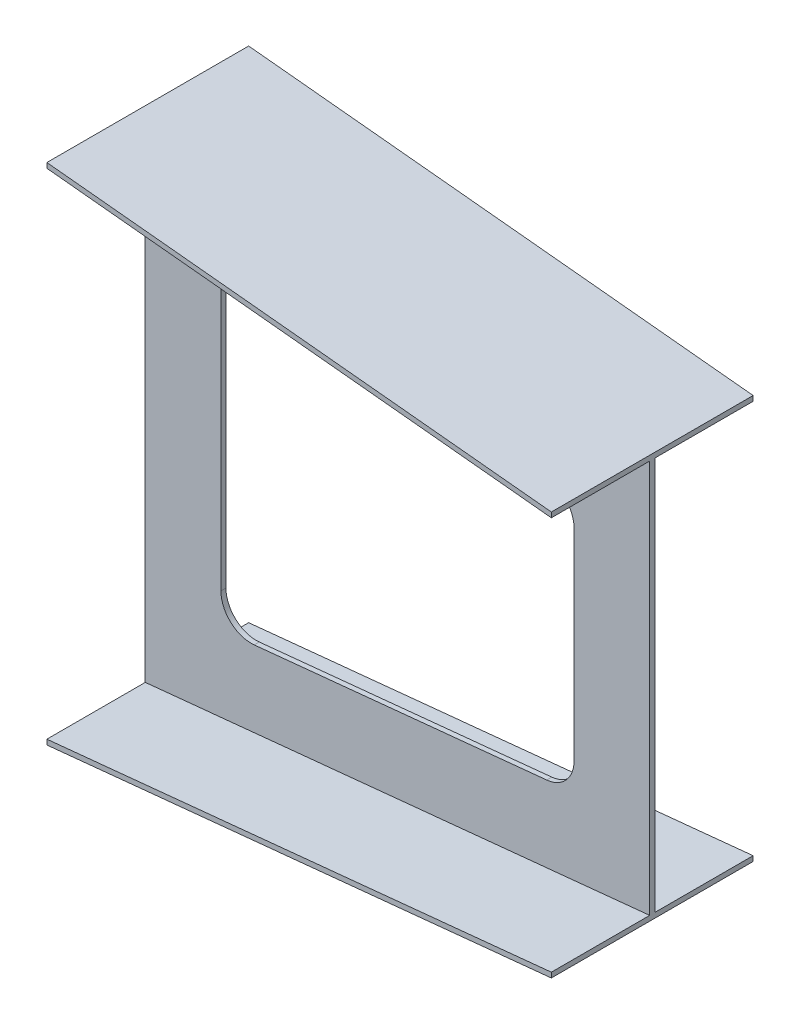
SolidWorks part; units mm, degrees
ref_plane "Front Plane" through (0, 0, 0) normal (0, 0, 1) x (1, 0, 0)
ref_plane "Top Plane" through (0, 0, 0) normal (0, 1, 0) x (1, 0, 0)
ref_plane "Right Plane" through (0, 0, 0) normal (1, 0, 0) x (0, 0, -1)
sketch "Sketch1" plane through (0, 0, 0) normal (1, 0, 0) x (0, 0, -1)
  line L1 (-205, 500) -> (195, 500)
  line L2 (-205, 500) -> (-205, 490)
  line L4 (195, 500) -> (195, 490)
  line L6 (-205, -490) -> (-205, -500)
  line L7 (-205, -500) -> (195, -500)
  line L8 (195, -490) -> (195, -500)
  line L15 (-205, -490) -> (-10, -490)
  line L16 (-5, 490) -> (-5, -490) construction
  line L18 (-205, 490) -> (-10, 490)
  line L19 (0, 0) -> (192.2403, 0) construction
  line L21 (-10, 490) -> (-10, -490)
  line L23 (0, 490) -> (0, -490)
  line L27 (0, 490) -> (195, 490)
  line L28 (0, -490) -> (195, -490)
  dimension "D1" = 400
  dimension "D2" = 10
  dimension "D3" = 1000
  dimension "D4" = 10
ref_plane "Plane2" through (1000, 0, 0) normal (1, 0, 0) x (0, 0, -1)
sketch "Sketch4" plane through (1000, 0, -1000) normal (-1, 0, 0) x (0, 0, 1)
  line L1 (805, 400) -> (1205, 400)
  line L2 (805, 400) -> (805, 390)
  line L4 (1205, 400) -> (1205, 390)
  line L6 (805, -390) -> (805, -400)
  line L7 (805, -400) -> (1205, -400)
  line L8 (1205, -390) -> (1205, -400)
  line L15 (805, -390) -> (1000, -390)
  line L16 (1005, 390) -> (1005, -390) construction
  line L18 (805, 390) -> (1000, 390)
  line L19 (1010, -390) -> (1205, -390)
  line L21 (1000, 390) -> (1000, -390)
  line L23 (1010, 390) -> (1010, -390)
  line L24 (1010, 390) -> (1205, 390)
  line L26 (1010, 490) -> (1010, -490) construction
  line L27 (1000, 0) -> (820.2065, 0) construction
  dimension "D1" = 400
  dimension "D2" = 10
  dimension "D3" = 800
  dimension "D4" = 10
loft "Loft4" add profiles "Sketch1", "Sketch4" connector at (0, 490, 10) connector at (1000, 390, 10)
sketch "Sketch6" plane through (0, 0, 10) normal (0, 0, 1) x (1, 0, 0)
  line L8 (150, -324.2519) -> (850, -254.2519)
  line L9 (850, -254.2519) -> (850, 254.2519)
  line L10 (850, 254.2519) -> (150, 324.2519)
  line L11 (150, 324.2519) -> (150, -324.2519)
  line L12 (215.9702, -317.6548) -> (795.9702, -259.6548)
  line L13 (850, -199.9526) -> (850, 199.9526)
  line L14 (795.9702, 259.6548) -> (215.9702, 317.6548)
  line L15 (150, 257.9526) -> (150, -257.9526)
  arc A0 (150, -257.9526) -> (215.9702, -317.6548) centre (210, -257.9526) ccw
  arc A1 (850, 199.9526) -> (795.9702, 259.6548) centre (790, 199.9526) ccw
  arc A2 (850, -199.9526) -> (795.9702, -259.6548) centre (790, -199.9526) cw
  arc A3 (150, 257.9526) -> (215.9702, 317.6548) centre (210, 257.9526) cw
  dimension "D2" = 60
  dimension "D1" = 150
extrude "Cut-Extrude1" cut sketch "Sketch6" against normal blind 10
equation "\"ANS_h4\"=800"
equation "\"D3@Sketch4\"=\"ANS_h4\""
equation "\"ANS_w4\"=400"
equation "\"D1@Sketch4\"=\"ANS_w4\""
equation "\"ANS_h5\"=1000"
equation "\"D3@Sketch1\"=\"ANS_h5\""
equation "\"ANS_w5\"=400"
equation "\"D1@Sketch1\"=\"ANS_w5\""
